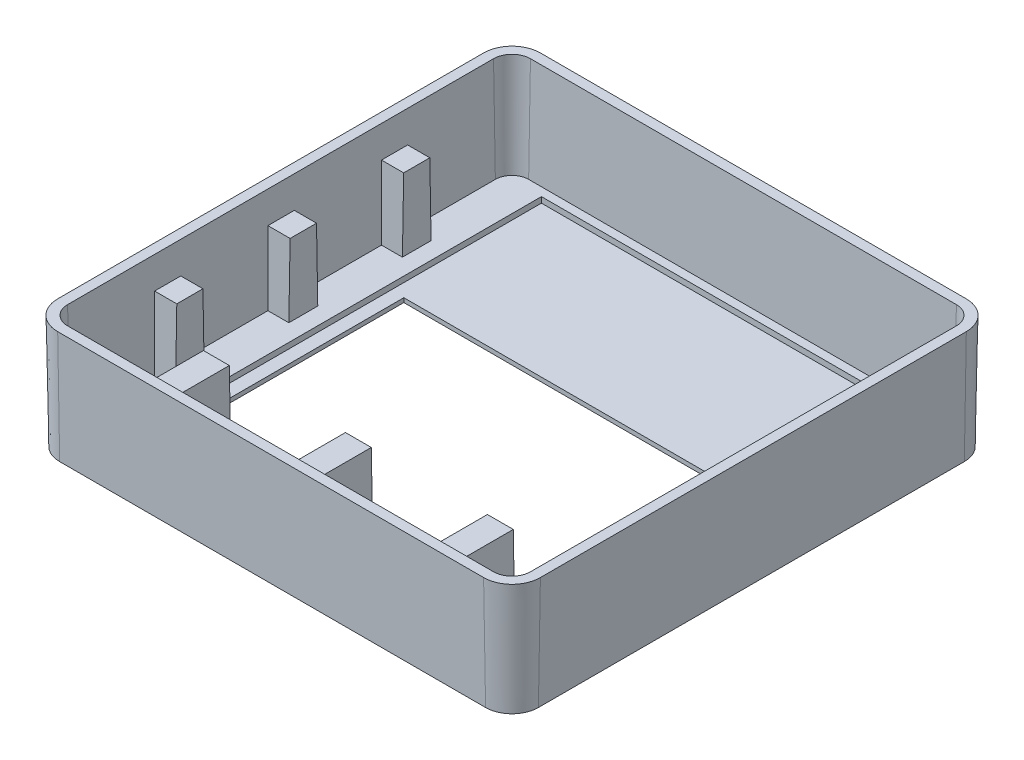
SolidWorks part; units mm, degrees
material "ABS"
ref_plane "Front Plane" through (0, 0, 0) normal (0, 0, 1) x (1, 0, 0)
ref_plane "Top Plane" through (0, 0, 0) normal (0, 1, 0) x (1, 0, 0)
ref_plane "Right Plane" through (0, 0, 0) normal (1, 0, 0) x (0, 0, -1)
sketch "Sketch1" plane through (0, 0, 0) normal (0, 1, 0) x (1, 0, 0)
  line L1 (-7.5, -8.5) -> (7.5, -8.5)
  line L2 (-8.5, -7.5) -> (-8.5, 7.5)
  line L3 (-7.5, 8.5) -> (7.5, 8.5)
  line L4 (8.5, -7.5) -> (8.5, 7.5)
  line L5 (-8.5, -8.5) -> (8.5, 8.5) construction
  line L6 (-8.5, 8.5) -> (8.5, -8.5) construction
  arc A0 (-8.5, 7.5) -> (-7.5, 8.5) centre (-7.5, 7.5) cw
  arc A1 (8.5, 7.5) -> (7.5, 8.5) centre (7.5, 7.5) ccw
  arc A2 (8.5, -7.5) -> (7.5, -8.5) centre (7.5, -7.5) cw
  arc A3 (-7.5, -8.5) -> (-8.5, -7.5) centre (-7.5, -7.5) cw
  point P0 (0, 0)
  dimension "D3" = 1
  dimension "D1" = 17
  dimension "D2" = 17
extrude "Boss-Extrude1" add sketch "Sketch1" against normal blind 4 draft 1
shell "Shell1" thickness 0.35 removed face at (0, 0, 0)
sketch "Sketch2" plane through (0, -4, 0) normal (0, -1, 0) x (1, 0, 0)
  line L0 (-7.5, 8.5) -> (7.5, 8.5) construction
  line L1 (-6.29, 4.5) -> (6.29, 4.5)
  line L2 (-6.29, 4.5) -> (-6.29, -2.48)
  line L3 (-6.29, -2.48) -> (6.29, -2.48)
  line L4 (6.29, 4.5) -> (6.29, -2.48)
  point P0 (0, 0)
  dimension "D1" = 4
  dimension "D2" = 6.98
extrude "Cut-Extrude1" cut sketch "Sketch2" against normal blind 2
sketch "Sketch3" plane through (0, -3.65, 0) normal (0, 1, 0) x (1, 0, 0)
  line L1 (6.75, 7.7862) -> (-6.75, 7.7862)
  line L2 (6.75, 7.7862) -> (6.75, -5.31)
  line L3 (6.75, -5.31) -> (-6.75, -5.31)
  line L4 (-6.75, 7.7862) -> (-6.75, -5.31)
  line L5 (6.29, 2.48) -> (6.29, -4.5) construction
  line L6 (-6.29, -4.5) -> (-6.29, 2.48) construction
  line L8 (6.29, -4.5) -> (-6.29, -4.5) construction
  line L9 (7.5, 8.0862) -> (-7.5, 8.0862) construction
  point P0 (0, 0)
  dimension "D1" = 0.81
  dimension "D2" = 0.46
  dimension "D3" = 0.46
  dimension "D4" = 0.3
extrude "Cut-Extrude2" cut sketch "Sketch3" against normal blind 0.2
ref_plane "Plane1" through (0, -1.2, 0) normal (0, -1, 0) x (-1, 0, 0)
ref_plane "Plane4" through (7.35, 0, 0) normal (-1, 0, 0) x (0, 0, 1)
sketch "Sketch11" plane through (7.35, 0, 0) normal (-1, 0, 0) x (0, 0, 1)
  line L0 (-9.35, -1.2) -> (9.35, -1.2) construction
  line L1 (-0.4555, -1.1) -> (0.4651, -1.1)
  line L3 (-0.5, -3.65) -> (0.5096, -3.65)
  line L5 (-7.5, -3.65) -> (7.5, -3.65) construction
  line L7 (0.5096, -3.65) -> (0.4651, -1.1)
  line L8 (-0.5, -3.65) -> (-0.4555, -1.1)
  dimension "D1" = 0.1
  dimension "D2" = 89
  dimension "D3" = 89
extrude "Boss-Extrude3" add sketch "Sketch11" against normal up to surface (0.7362 mm away) up to face at (8.1181, -1.825, 0)
ref_plane "Plane5" through (-7.35, 0, 0) normal (1, 0, 0) x (0, 0, -1)
sketch "Sketch13" plane through (-7.35, 0, 0) normal (1, 0, 0) x (0, 0, -1)
  line L0 (-9.35, -1.2) -> (9.35, -1.2) construction
  line L3 (-0.5, -3.65) -> (0.5096, -3.65)
  line L6 (0.5096, -3.65) -> (0.4651, -1.1)
  line L7 (-0.5, -3.65) -> (-0.4555, -1.1)
  line L8 (-0.4555, -1.1) -> (0.4651, -1.1)
  dimension "D1" = 0.1
  dimension "D2" = 89
  dimension "D3" = 89
extrude "Boss-Extrude4" add sketch "Sketch13" against normal up to surface (0.7362 mm away) up to face at (-8.1181, -1.825, 0)
ref_plane "Plane6" through (0, 0, 0) normal (1, 0, 0.0016) x (0.0016, 0, -1)
pattern_linear "LPattern2" count 2 spacing 4 along (0, 0, 1) of "Boss-Extrude3"
mirror "Mirror4" about plane through (0, 0, 0) normal (0, 0, 1) of "LPattern2"
pattern_linear "LPattern3" count 2 spacing 4 along (0, 0, 1) of "Boss-Extrude4"
mirror "Mirror5" about plane through (0, 0, 0) normal (0, 0, 1) of "LPattern3"
ref_plane "Plane7" through (0, 0, 5.41) normal (0, 0, 1) x (1, 0, 0)
sketch "Sketch16" plane through (0, 0, 5.41) normal (0, 0, 1) x (1, 0, 0)
  line L0 (-0.5, -3.65) -> (0.5, -3.65)
  line L1 (-7.5, -3.65) -> (7.5, -3.65) construction
  line L2 (0, -55) -> (0, 55) construction
  line L3 (-0.4555, -1.1) -> (0.4555, -1.1)
  line L5 (-0.5, -3.65) -> (-0.4555, -1.1)
  line L6 (0.5, -3.65) -> (0.4555, -1.1)
  line L7 (-9.35, -1.2) -> (9.35, -1.2) construction
  point P9 (0, -1.1)
  dimension "D1" = 0.5
  dimension "D2" = 0.5
  dimension "D3" = 89
  dimension "D4" = 89
  dimension "D5" = 0.1
extrude "Boss-Extrude5" add sketch "Sketch16" along normal up to surface (2.6762 mm away) up to face at (0, -1.825, 8.1181)
pattern_linear "LPattern4" count 2 spacing 5 along (1, 0, 0) of "Boss-Extrude5"
mirror "Mirror6" about plane through (0, 0, 0) normal (1, 0, 0) of "LPattern4"
